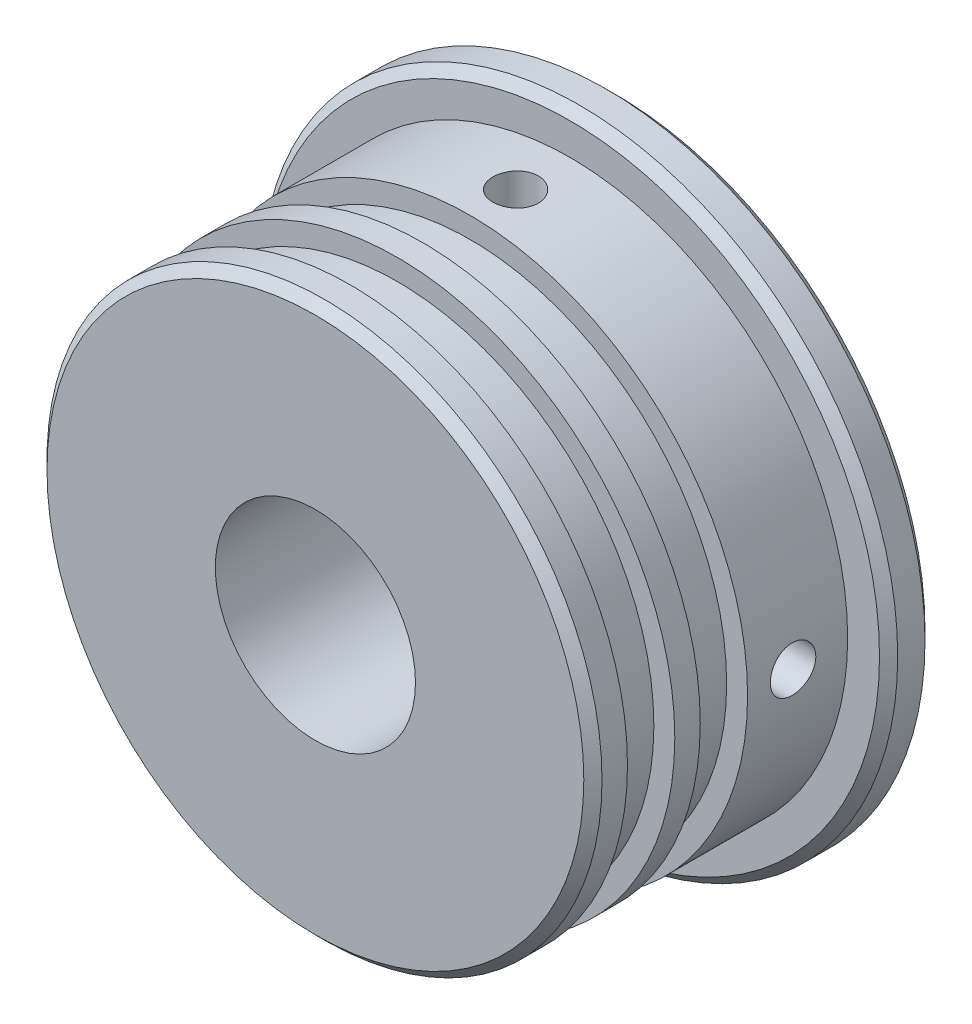
SolidWorks part; units mm, degrees
ref_plane "Спереди" through (0, 0, 0) normal (0, 0, 1) x (1, 0, 0)
ref_plane "Сверху" through (0, 0, 0) normal (0, 1, 0) x (1, 0, 0)
ref_plane "Справа" through (0, 0, 0) normal (1, 0, 0) x (0, 0, -1)
other "Configuration Table"
sketch "Эскиз1" plane through (0, 0, 0) normal (0, 0, 1) x (1, 0, 0)
  circle A0 centre (0, 0) radius 17.5
  circle A1 centre (0, 0) radius 15.25
  circle A2 centre (0, 0) radius 14.1
  circle A3 centre (0, 0) radius 5.5
  dimension "D1" = 35
  dimension "D2" = 30.5
  dimension "D3" = 28.2
  dimension "D4" = 11
extrude "Бобышка-Вытянуть1" add sketch "Эскиз1" against normal blind 2.5 contours A0 A1 | A1 A2 | A2 region at (-17.005, 0, 0) region at (-14.8187, 0, 0) region at (-13.7012, 0, 0)
extrude "Бобышка-Вытянуть2" add sketch "Эскиз1<3>" along normal blind 14 contours A1 A2 | A2 region at (-14.8187, 0, 0) region at (-13.7012, 0, 0)
sketch "Эскиз1<3>" plane through (0, 0, 0) normal (0, 0, 1) x (1, 0, 0) same geometry as "Эскиз1"
extrude "Вырез-Вытянуть1" cut sketch "Эскиз1<4>" along normal blind 2.6 from offset 5.5 contours A1 A2 region at (-14.8187, 0, 0)
sketch "Эскиз1<4>" plane through (0, 0, 0) normal (0, 0, 1) x (1, 0, 0) same geometry as "Эскиз1"
extrude "Вырез-Вытянуть2" cut sketch "Эскиз1<5>" along normal blind 2.6 from offset 9.5 contours A1 A2 region at (-14.8187, 0, 0)
sketch "Эскиз1<5>" plane through (0, 0, 0) normal (0, 0, 1) x (1, 0, 0) same geometry as "Эскиз1"
chamfer "Фаска1" distance 0.5 angle 45 3 edges at (15.25, 0, 14) (17.5, 0, 0) (17.5, 0, -2.5)
sketch "Эскиз2" plane through (0, 0, -2.5) normal (0, 0, -1) x (-1, 0, 0)
  circle A0 centre (0, 0) radius 6
  dimension "D1" = 12
extrude "Вырез-Вытянуть3" cut sketch "Эскиз2" against normal blind 2.5
sketch "Эскиз3" plane through (0, 0, 0) normal (0, 1, 0) x (1, 0, 0)
  line L0 (0, 0) -> (0, 5.0181)
  circle A0 centre (0, -3) radius 1.25
  dimension "D1" = 2.5
  dimension "D2" = 3
extrude "Вырез-Вытянуть4" cut sketch "Эскиз3" along normal blind 10 from offset 10 contours A0 region at (0, 0, 3)
pattern_circular "Круговой массив1" count 4 every 90 about axis through (0, 0, 0) along (0, 0, -1) of "Вырез-Вытянуть4"
